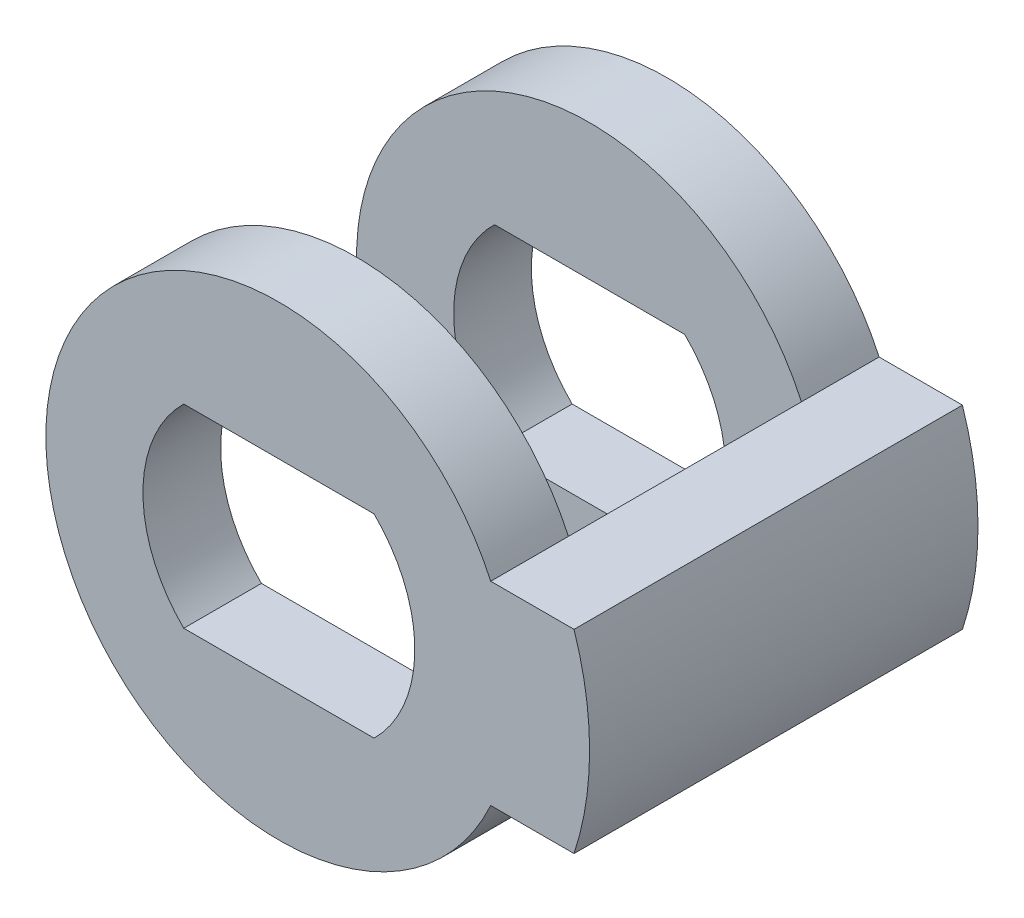
SolidWorks part; units mm, degrees
ref_plane "Front Plane" through (0, 0, 0) normal (0, 0, 1) x (1, 0, 0)
ref_plane "Top Plane" through (0, 0, 0) normal (0, 1, 0) x (1, 0, 0)
ref_plane "Right Plane" through (0, 0, 0) normal (1, 0, 0) x (0, 0, -1)
sketch "Sketch1" plane through (0, 0, 0) normal (0, 0, 1) x (1, 0, 0)
  line L0 (-4.899, 5) -> (4.899, 5)
  line L1 (-4.899, -5) -> (4.899, -5)
  line L2 (0, 5) -> (0, -5) construction
  line L3 (4.899, -5) -> (10.9087, -5) construction
  line L4 (4.899, 5) -> (10.9087, 5) construction
  line L5 (10.9087, -5) -> (15.1987, -5)
  line L6 (10.9087, 5) -> (15.1987, 5)
  circle A0 centre (0, 0) radius 12
  circle A1 centre (0, 0) radius 7
  circle A2 centre (0, 0) radius 16
  point P11 (0, 0)
  dimension "D2" = 14
  dimension "D3" = 24
  dimension "D4" = 4
  dimension "D1" = 10
extrude "Boss-Extrude2" add sketch "Sketch1" along normal blind 10 and the other way blind 10 contours A0 A1 | L1 A1 | L0 A1 | L5 A2 L6 A0 region at (0, 5.8107, 0) region at (0, -5.8107, 0) region at (13.6835, 0, 0) region at (-11.6606, 0, 0)
sketch "Sketch3" plane through (0, 0, 0) normal (0, 0, 1) x (1, 0, 0)
  circle A0 centre (0, 0) radius 12
  arc A1 (10.9087, 5) -> (10.9087, -5) centre (0, 0) ccw construction
extrude "Cut-Extrude1" cut sketch "Sketch3" against normal blind 6 and the other way blind 6
